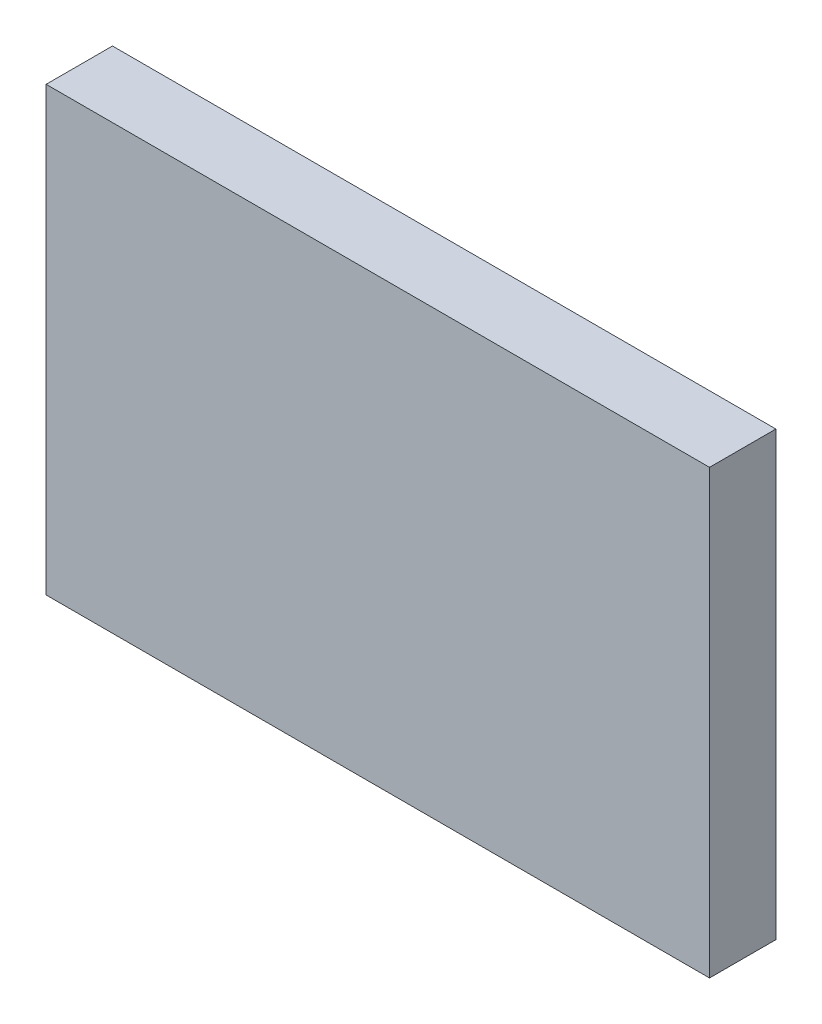
SolidWorks part; units mm, degrees
ref_plane "Ebene vorne" through (0, 0, 0) normal (0, 0, 1) x (1, 0, 0)
ref_plane "Ebene oben" through (0, 0, 0) normal (0, 1, 0) x (1, 0, 0)
ref_plane "Ebene rechts" through (0, 0, 0) normal (1, 0, 0) x (0, 0, -1)
sketch "Skizze1" plane through (0, 0, 0) normal (0, 0, 1) x (1, 0, 0)
  line L1 (-15, -10) -> (15, -10)
  line L2 (-15, -10) -> (-15, 10)
  line L3 (-15, 10) -> (15, 10)
  line L4 (15, -10) -> (15, 10)
  line L5 (-15, -10) -> (15, 10) construction
  line L6 (-15, 10) -> (15, -10) construction
  point P0 (0, 0)
  dimension "D1" = 30
  dimension "D2" = 20
extrude "Aufsatz-Linear austragen1" add sketch "Skizze1" along normal blind 3
ref_plane "Ebene1" through (0, 0, 0) normal (-1, 0, 0) x (0, 0, 1)
ref_plane "Ebene2" through (0, 0, 3) normal (0, 0, 1) x (1, 0, 0)
ref_plane "Ebene3" through (0, 10, 0) normal (0, 1, 0) x (1, 0, 0)
ref_axis "Achse1" through (16.5, 10, 3) along (-1, 0, 0)
ref_point "Punkt1"
